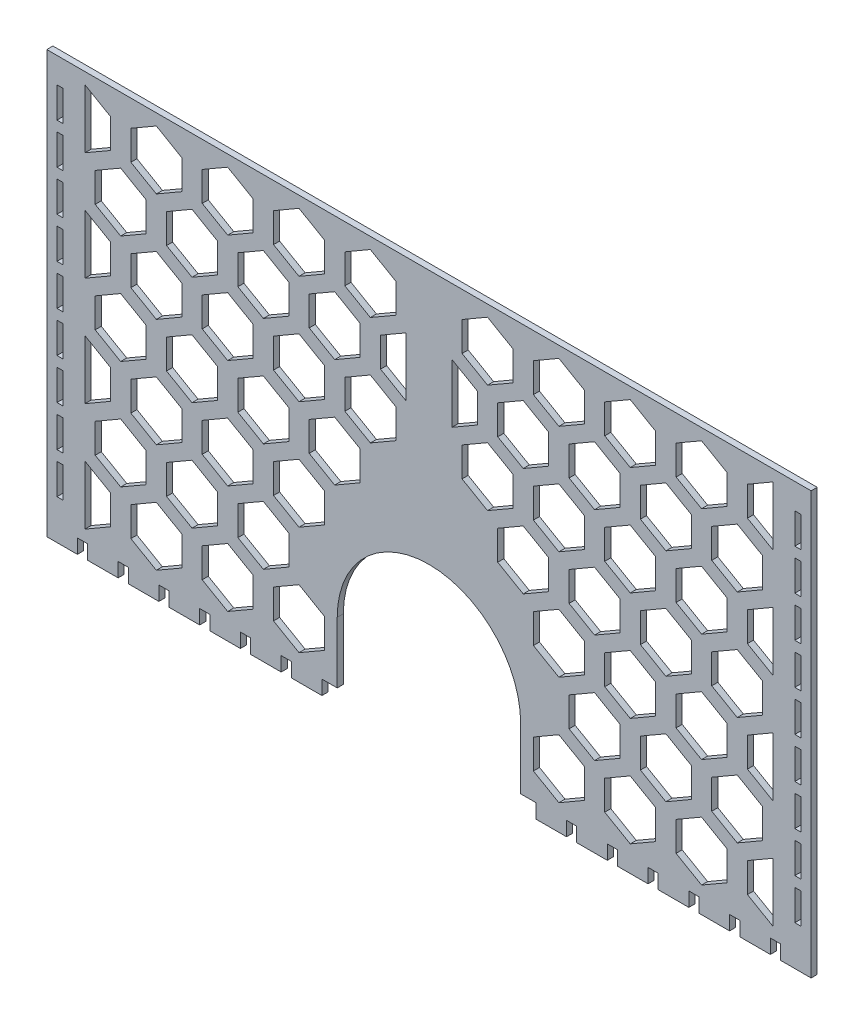
SolidWorks part; units mm, degrees
material "Brass"
ref_plane "Front Plane" through (0, 0, 0) normal (0, 0, 1) x (1, 0, 0)
ref_plane "Top Plane" through (0, 0, 0) normal (0, 1, 0) x (1, 0, 0)
ref_plane "Right Plane" through (0, 0, 0) normal (1, 0, 0) x (0, 0, -1)
sketch "Sketch1" plane through (0, 0, 0) normal (0, 0, 1) x (1, 0, 0)
  line L0 (0, 100) -> (0, -100) construction
  line L2 (-187.5, -100) -> (-187.5, 100)
  line L3 (-187.5, 100) -> (187.5, 100)
  line L4 (187.5, -100) -> (187.5, 100)
  line L6 (-187.5, 0) -> (187.5, 0) construction
  line L11 (-187.5, -100) -> (187.5, -100)
  line L13 (-187.5, 0) -> (-182.5, 0) construction
  line L15 (-45, -70) -> (-45, -100)
  line L16 (-45, -100) -> (45, -100)
  line L17 (45, -70) -> (45, -100)
  line L18 (-179.5, 7.5) -> (-182.5, 7.5)
  line L19 (-179.5, 7.5) -> (-179.5, -7.5)
  line L20 (-179.5, -7.5) -> (-182.5, -7.5)
  line L21 (-182.5, 7.5) -> (-182.5, -7.5)
  line L22 (-179.5, 27.5) -> (-179.5, 12.5)
  line L23 (-179.5, 27.5) -> (-182.5, 27.5)
  line L24 (-182.5, 27.5) -> (-182.5, 12.5)
  line L25 (-179.5, 12.5) -> (-182.5, 12.5)
  line L26 (-179.5, 47.5) -> (-179.5, 32.5)
  line L27 (-179.5, 47.5) -> (-182.5, 47.5)
  line L28 (-182.5, 47.5) -> (-182.5, 32.5)
  line L29 (-179.5, 32.5) -> (-182.5, 32.5)
  line L30 (-179.5, 67.5) -> (-179.5, 52.5)
  line L31 (-179.5, 67.5) -> (-182.5, 67.5)
  line L32 (-182.5, 67.5) -> (-182.5, 52.5)
  line L33 (-179.5, 52.5) -> (-182.5, 52.5)
  line L34 (-179.5, 87.5) -> (-179.5, 72.5)
  line L35 (-179.5, 87.5) -> (-182.5, 87.5)
  line L36 (-182.5, 87.5) -> (-182.5, 72.5)
  line L37 (-179.5, 72.5) -> (-182.5, 72.5)
  line L38 (-179.5, 7.5) -> (-179.5, -7.5)
  line L39 (-179.5, 7.5) -> (-182.5, 7.5)
  line L40 (-182.5, 7.5) -> (-182.5, -7.5)
  line L41 (-179.5, -7.5) -> (-182.5, -7.5)
  line L42 (-179.5, 27.5) -> (-179.5, 12.5)
  line L43 (-179.5, 27.5) -> (-182.5, 27.5)
  line L44 (-182.5, 27.5) -> (-182.5, 12.5)
  line L45 (-179.5, 12.5) -> (-182.5, 12.5)
  line L46 (-179.5, 47.5) -> (-179.5, 32.5)
  line L47 (-179.5, 47.5) -> (-182.5, 47.5)
  line L48 (-182.5, 47.5) -> (-182.5, 32.5)
  line L49 (-179.5, 32.5) -> (-182.5, 32.5)
  line L50 (-179.5, 67.5) -> (-179.5, 52.5)
  line L51 (-179.5, 67.5) -> (-182.5, 67.5)
  line L52 (-182.5, 67.5) -> (-182.5, 52.5)
  line L53 (-179.5, 52.5) -> (-182.5, 52.5)
  line L54 (-179.5, -12.5) -> (-179.5, -27.5)
  line L55 (-179.5, -12.5) -> (-182.5, -12.5)
  line L56 (-182.5, -12.5) -> (-182.5, -27.5)
  line L57 (-179.5, -27.5) -> (-182.5, -27.5)
  line L58 (-179.5, 7.5) -> (-179.5, -7.5)
  line L59 (-179.5, 7.5) -> (-182.5, 7.5)
  line L60 (-182.5, 7.5) -> (-182.5, -7.5)
  line L61 (-179.5, -7.5) -> (-182.5, -7.5)
  line L62 (-179.5, 27.5) -> (-179.5, 12.5)
  line L63 (-179.5, 27.5) -> (-182.5, 27.5)
  line L64 (-182.5, 27.5) -> (-182.5, 12.5)
  line L65 (-179.5, 12.5) -> (-182.5, 12.5)
  line L66 (-179.5, 47.5) -> (-179.5, 32.5)
  line L67 (-179.5, 47.5) -> (-182.5, 47.5)
  line L68 (-182.5, 47.5) -> (-182.5, 32.5)
  line L69 (-179.5, 32.5) -> (-182.5, 32.5)
  line L70 (-179.5, -32.5) -> (-179.5, -47.5)
  line L71 (-179.5, -32.5) -> (-182.5, -32.5)
  line L72 (-182.5, -32.5) -> (-182.5, -47.5)
  line L73 (-179.5, -47.5) -> (-182.5, -47.5)
  line L74 (-179.5, -12.5) -> (-179.5, -27.5)
  line L75 (-179.5, -12.5) -> (-182.5, -12.5)
  line L76 (-182.5, -12.5) -> (-182.5, -27.5)
  line L77 (-179.5, -27.5) -> (-182.5, -27.5)
  line L78 (-179.5, 7.5) -> (-179.5, -7.5)
  line L79 (-179.5, 7.5) -> (-182.5, 7.5)
  line L80 (-182.5, 7.5) -> (-182.5, -7.5)
  line L81 (-179.5, -7.5) -> (-182.5, -7.5)
  line L82 (-179.5, 27.5) -> (-179.5, 12.5)
  line L83 (-179.5, 27.5) -> (-182.5, 27.5)
  line L84 (-182.5, 27.5) -> (-182.5, 12.5)
  line L85 (-179.5, 12.5) -> (-182.5, 12.5)
  line L86 (-179.5, -52.5) -> (-179.5, -67.5)
  line L87 (-179.5, -52.5) -> (-182.5, -52.5)
  line L88 (-182.5, -52.5) -> (-182.5, -67.5)
  line L89 (-179.5, -67.5) -> (-182.5, -67.5)
  line L90 (-179.5, -32.5) -> (-179.5, -47.5)
  line L91 (-179.5, -32.5) -> (-182.5, -32.5)
  line L92 (-182.5, -32.5) -> (-182.5, -47.5)
  line L93 (-179.5, -47.5) -> (-182.5, -47.5)
  line L94 (-179.5, -12.5) -> (-179.5, -27.5)
  line L95 (-179.5, -12.5) -> (-182.5, -12.5)
  line L96 (-182.5, -12.5) -> (-182.5, -27.5)
  line L97 (-179.5, -27.5) -> (-182.5, -27.5)
  line L98 (-179.5, 7.5) -> (-179.5, -7.5)
  line L99 (-179.5, 7.5) -> (-182.5, 7.5)
  line L100 (-182.5, 7.5) -> (-182.5, -7.5)
  line L101 (-179.5, -7.5) -> (-182.5, -7.5)
  line L102 (-179.5, -12.5) -> (-179.5, -27.5)
  line L103 (-179.5, -12.5) -> (-182.5, -12.5)
  line L104 (-182.5, -12.5) -> (-182.5, -27.5)
  line L105 (-179.5, -27.5) -> (-182.5, -27.5)
  line L106 (-179.5, -32.5) -> (-179.5, -47.5)
  line L107 (-179.5, -32.5) -> (-182.5, -32.5)
  line L108 (-182.5, -32.5) -> (-182.5, -47.5)
  line L109 (-179.5, -47.5) -> (-182.5, -47.5)
  line L110 (-179.5, -52.5) -> (-179.5, -67.5)
  line L111 (-179.5, -52.5) -> (-182.5, -52.5)
  line L112 (-182.5, -52.5) -> (-182.5, -67.5)
  line L113 (-179.5, -67.5) -> (-182.5, -67.5)
  line L114 (-179.5, -72.5) -> (-179.5, -87.5)
  line L115 (-179.5, -72.5) -> (-182.5, -72.5)
  line L116 (-182.5, -72.5) -> (-182.5, -87.5)
  line L117 (-179.5, -87.5) -> (-182.5, -87.5)
  line L118 (187.5, 0) -> (182.5, 0) construction
  line L119 (182.5, 27.5) -> (179.5, 27.5)
  line L120 (179.5, 27.5) -> (179.5, 12.5)
  line L121 (182.5, 7.5) -> (179.5, 7.5)
  line L122 (182.5, 7.5) -> (182.5, -7.5)
  line L123 (182.5, -7.5) -> (179.5, -7.5)
  line L124 (179.5, 7.5) -> (179.5, -7.5)
  line L221 (182.5, 12.5) -> (179.5, 12.5)
  line L222 (182.5, 27.5) -> (182.5, 12.5)
  line L223 (182.5, 47.5) -> (179.5, 47.5)
  line L224 (179.5, 47.5) -> (179.5, 32.5)
  line L225 (182.5, 32.5) -> (179.5, 32.5)
  line L226 (182.5, 47.5) -> (182.5, 32.5)
  line L227 (182.5, 67.5) -> (179.5, 67.5)
  line L228 (179.5, 67.5) -> (179.5, 52.5)
  line L229 (182.5, 52.5) -> (179.5, 52.5)
  line L230 (182.5, 67.5) -> (182.5, 52.5)
  line L231 (182.5, 87.5) -> (179.5, 87.5)
  line L232 (179.5, 87.5) -> (179.5, 72.5)
  line L233 (182.5, 72.5) -> (179.5, 72.5)
  line L234 (182.5, 87.5) -> (182.5, 72.5)
  line L235 (182.5, -12.5) -> (179.5, -12.5)
  line L236 (179.5, -12.5) -> (179.5, -27.5)
  line L237 (182.5, -27.5) -> (179.5, -27.5)
  line L238 (182.5, -12.5) -> (182.5, -27.5)
  line L239 (182.5, -32.5) -> (179.5, -32.5)
  line L240 (179.5, -32.5) -> (179.5, -47.5)
  line L241 (182.5, -47.5) -> (179.5, -47.5)
  line L242 (182.5, -32.5) -> (182.5, -47.5)
  line L243 (182.5, -52.5) -> (179.5, -52.5)
  line L244 (179.5, -52.5) -> (179.5, -67.5)
  line L245 (182.5, -67.5) -> (179.5, -67.5)
  line L246 (182.5, -52.5) -> (182.5, -67.5)
  line L247 (182.5, -72.5) -> (179.5, -72.5)
  line L248 (179.5, -72.5) -> (179.5, -87.5)
  line L249 (182.5, -87.5) -> (179.5, -87.5)
  line L250 (182.5, -72.5) -> (182.5, -87.5)
  arc A1 (45, -70) -> (-45, -70) centre (0, -70) ccw
  circle A2 centre (0, -70) radius 40 construction
  point P0 (0, 0)
  point P16 (0, 0)
  point P17 (-182.5, 0)
  point P121 (182.5, 0)
  point P122 (181, 7.5)
  dimension "D3" = 90
  dimension "D5" = 30
  dimension "D4" = 142.5
  dimension "D6" = 80
  dimension "D2" = 187.5
  dimension "D7" = 15
  dimension "D8" = 3
  dimension "D9" = 5
  dimension "D12" = 5
  dimension "D13" = 5
  dimension "D14" = 200
  dimension "D15" = 15
  dimension "D16" = 3
  dimension "D17" = 5
  dimension "D18" = 5
  dimension "D19" = 5
  dimension "D21" = 5
  dimension "D10" = 5
  dimension "D11" = 5
  dimension "D20" = 5
extrude "Boss-Extrude1" add sketch "Sketch1" along normal blind 3 contours A1 L17 L11 L4 L3 L2 L15 region at (0, 5.73, 0)
sketch "Sketch7" plane through (0, -100, 0) normal (0, -1, 0) x (1, 0, 0)
  line L0 (-187.5, 0) -> (-45, 0) construction
  line L1 (-187.5, 3) -> (-172.5, 3)
  line L2 (-187.5, 3) -> (-187.5, 0)
  line L3 (-187.5, 0) -> (-172.5, 0)
  line L4 (-172.5, 3) -> (-172.5, 0)
  line L5 (-167.5, 3) -> (-167.5, 0)
  line L6 (-167.5, 3) -> (-152.5, 3)
  line L7 (-152.5, 3) -> (-152.5, 0)
  line L8 (-167.5, 0) -> (-152.5, 0)
  line L9 (-147.5, 3) -> (-147.5, 0)
  line L10 (-147.5, 3) -> (-132.5, 3)
  line L11 (-132.5, 3) -> (-132.5, 0)
  line L12 (-147.5, 0) -> (-132.5, 0)
  line L13 (-127.5, 3) -> (-127.5, 0)
  line L14 (-127.5, 3) -> (-112.5, 3)
  line L15 (-112.5, 3) -> (-112.5, 0)
  line L16 (-127.5, 0) -> (-112.5, 0)
  line L17 (-107.5, 3) -> (-107.5, 0)
  line L18 (-107.5, 3) -> (-92.5, 3)
  line L19 (-92.5, 3) -> (-92.5, 0)
  line L20 (-107.5, 0) -> (-92.5, 0)
  line L21 (-87.5, 3) -> (-87.5, 0)
  line L22 (-87.5, 3) -> (-72.5, 3)
  line L23 (-72.5, 3) -> (-72.5, 0)
  line L24 (-87.5, 0) -> (-72.5, 0)
  line L25 (-67.5, 3) -> (-67.5, 0)
  line L26 (-67.5, 3) -> (-52.5, 3)
  line L27 (-52.5, 3) -> (-52.5, 0)
  line L28 (-67.5, 0) -> (-52.5, 0)
  dimension "D1" = 15
  dimension "D3" = 5
  dimension "D2" = 7
extrude "Boss-Extrude2" add sketch "Sketch7" along normal blind 7
sketch "Sketch8" plane through (0, -100, 0) normal (0, -1, 0) x (1, 0, 0)
  line L0 (45, 3) -> (187.5, 3) construction
  line L1 (187.5, 0) -> (172.5, 0)
  line L2 (187.5, 0) -> (187.5, 3)
  line L3 (187.5, 3) -> (172.5, 3)
  line L4 (172.5, 0) -> (172.5, 3)
  line L5 (167.5, 0) -> (167.5, 3)
  line L6 (167.5, 0) -> (152.5, 0)
  line L7 (152.5, 0) -> (152.5, 3)
  line L8 (167.5, 3) -> (152.5, 3)
  line L9 (147.5, 0) -> (147.5, 3)
  line L10 (147.5, 0) -> (132.5, 0)
  line L11 (132.5, 0) -> (132.5, 3)
  line L12 (147.5, 3) -> (132.5, 3)
  line L13 (127.5, 0) -> (127.5, 3)
  line L14 (127.5, 0) -> (112.5, 0)
  line L15 (112.5, 0) -> (112.5, 3)
  line L16 (127.5, 3) -> (112.5, 3)
  line L17 (107.5, 0) -> (107.5, 3)
  line L18 (107.5, 0) -> (92.5, 0)
  line L19 (92.5, 0) -> (92.5, 3)
  line L20 (107.5, 3) -> (92.5, 3)
  line L21 (87.5, 0) -> (87.5, 3)
  line L22 (87.5, 0) -> (72.5, 0)
  line L23 (72.5, 0) -> (72.5, 3)
  line L24 (87.5, 3) -> (72.5, 3)
  line L25 (67.5, 0) -> (67.5, 3)
  line L26 (67.5, 0) -> (52.5, 0)
  line L27 (52.5, 0) -> (52.5, 3)
  line L28 (67.5, 3) -> (52.5, 3)
  dimension "D1" = 15
  dimension "D3" = 5
  dimension "D2" = 7
extrude "Boss-Extrude3" add sketch "Sketch8" along normal blind 7
sketch "Sketch10" plane through (0, 0, 0) normal (0, 0, -1) x (-1, 0, 0)
  line L0 (-45, -100) -> (-45, 100) construction
  line L1 (187.5, 100) -> (-187.5, 100) construction
  line L2 (-45, 100) -> (-187.5, 100) construction
  line L3 (-187.5, 100) -> (-187.5, -100) construction
  line L4 (-187.5, -107) -> (-187.5, 100) construction
  line L5 (-187.5, -100) -> (-45, -100) construction
  line L6 (-116.25, 100) -> (-116.25, -100) construction
  line L7 (-98.75, -26.6506) -> (-98.75, -100) construction
  line L8 (-45, 0) -> (-187.5, 0) construction
  line L9 (-116.25, -14.4338) -> (-103.75, -7.2169)
  line L10 (-103.75, -7.2169) -> (-103.75, 7.2169)
  line L11 (-103.75, 7.2169) -> (-116.25, 14.4338)
  line L12 (-116.25, 14.4338) -> (-128.75, 7.2169)
  line L13 (-128.75, 7.2169) -> (-128.75, -7.2169)
  line L14 (-128.75, -7.2169) -> (-116.25, -14.4338)
  line L15 (-98.75, -100) -> (-98.75, 100) construction
  line L16 (-98.75, -12.2169) -> (-111.25, -19.4338)
  line L17 (-111.25, -19.4338) -> (-111.25, -33.8675)
  line L18 (-111.25, -33.8675) -> (-98.75, -41.0844)
  line L19 (-98.75, -41.0844) -> (-86.25, -33.8675)
  line L20 (-86.25, -33.8675) -> (-86.25, -19.4338)
  line L21 (-86.25, -19.4338) -> (-98.75, -12.2169)
  line L22 (-133.75, -100) -> (-133.75, 100) construction
  line L23 (-45, -26.6506) -> (-187.5, -26.6506) construction
  line L24 (-133.75, -41.0844) -> (-121.25, -33.8675)
  line L25 (-121.25, -33.8675) -> (-121.25, -19.4338)
  line L26 (-121.25, -19.4338) -> (-133.75, -12.2169)
  line L27 (-133.75, -12.2169) -> (-146.25, -19.4338)
  line L28 (-146.25, -19.4338) -> (-146.25, -33.8675)
  line L29 (-146.25, -33.8675) -> (-133.75, -41.0844)
  line L36 (187.5, -107) -> (187.5, 100) construction
  line L37 (-116.25, -67.735) -> (-103.75, -60.5181)
  line L38 (-103.75, -60.5181) -> (-103.75, -46.0844)
  line L39 (-103.75, -46.0844) -> (-116.25, -38.8675)
  line L40 (-116.25, -38.8675) -> (-128.75, -46.0844)
  line L41 (-128.75, -46.0844) -> (-128.75, -60.5181)
  line L42 (-128.75, -60.5181) -> (-116.25, -67.735)
  line L61 (-81.25, -14.4338) -> (-68.75, -7.2169)
  line L62 (-68.75, -7.2169) -> (-68.75, 7.2169)
  line L63 (-68.75, 7.2169) -> (-81.25, 14.4338)
  line L64 (-81.25, 14.4338) -> (-93.75, 7.2169)
  line L65 (-93.75, 7.2169) -> (-93.75, -7.2169)
  line L66 (-93.75, -7.2169) -> (-81.25, -14.4338)
  line L67 (-81.25, -67.735) -> (-68.75, -60.5181)
  line L68 (-68.75, -60.5181) -> (-68.75, -46.0844)
  line L69 (-68.75, -46.0844) -> (-81.25, -38.8675)
  line L70 (-81.25, -38.8675) -> (-93.75, -46.0844)
  line L71 (-93.75, -46.0844) -> (-93.75, -60.5181)
  line L72 (-93.75, -60.5181) -> (-81.25, -67.735)
  line L73 (-63.75, -41.0844) -> (-51.25, -33.8675)
  line L74 (-51.25, -33.8675) -> (-51.25, -19.4338)
  line L75 (-51.25, -19.4338) -> (-63.75, -12.2169)
  line L76 (-63.75, -12.2169) -> (-76.25, -19.4338)
  line L77 (-76.25, -19.4338) -> (-76.25, -33.8675)
  line L78 (-76.25, -33.8675) -> (-63.75, -41.0844)
  line L79 (-151.25, -14.4338) -> (-138.75, -7.2169)
  line L80 (-138.75, -7.2169) -> (-138.75, 7.2169)
  line L81 (-138.75, 7.2169) -> (-151.25, 14.4338)
  line L82 (-151.25, 14.4338) -> (-163.75, 7.2169)
  line L83 (-163.75, 7.2169) -> (-163.75, -7.2169)
  line L84 (-163.75, -7.2169) -> (-151.25, -14.4338)
  line L85 (-151.25, -67.735) -> (-138.75, -60.5181)
  line L86 (-138.75, -60.5181) -> (-138.75, -46.0844)
  line L87 (-138.75, -46.0844) -> (-151.25, -38.8675)
  line L88 (-151.25, -38.8675) -> (-163.75, -46.0844)
  line L89 (-163.75, -46.0844) -> (-163.75, -60.5181)
  line L90 (-163.75, -60.5181) -> (-151.25, -67.735)
  line L91 (-168.75, -41.0844) -> (-156.25, -33.8675)
  line L92 (-156.25, -33.8675) -> (-156.25, -19.4338)
  line L93 (-156.25, -19.4338) -> (-168.75, -12.2169)
  line L96 (-168.75, -12.2169) -> (-168.75, -41.0844)
  line L103 (-133.75, 12.2169) -> (-121.25, 19.4338)
  line L104 (-121.25, 19.4338) -> (-121.25, 33.8675)
  line L105 (-121.25, 33.8675) -> (-133.75, 41.0844)
  line L106 (-133.75, 41.0844) -> (-146.25, 33.8675)
  line L107 (-146.25, 33.8675) -> (-146.25, 19.4338)
  line L108 (-146.25, 19.4338) -> (-133.75, 12.2169)
  line L109 (-98.75, 12.2169) -> (-86.25, 19.4338)
  line L110 (-86.25, 19.4338) -> (-86.25, 33.8675)
  line L111 (-86.25, 33.8675) -> (-98.75, 41.0844)
  line L112 (-98.75, 41.0844) -> (-111.25, 33.8675)
  line L113 (-111.25, 33.8675) -> (-111.25, 19.4338)
  line L114 (-111.25, 19.4338) -> (-98.75, 12.2169)
  line L115 (-168.75, 12.2169) -> (-156.25, 19.4338)
  line L116 (-156.25, 19.4338) -> (-156.25, 33.8675)
  line L117 (-156.25, 33.8675) -> (-168.75, 41.0844)
  line L118 (-168.75, 41.0844) -> (-168.75, 12.2169)
  line L119 (-63.75, 12.2169) -> (-51.25, 19.4338)
  line L120 (-51.25, 19.4338) -> (-51.25, 33.8675)
  line L121 (-51.25, 33.8675) -> (-63.75, 41.0844)
  line L122 (-63.75, 41.0844) -> (-76.25, 33.8675)
  line L123 (-76.25, 33.8675) -> (-76.25, 19.4338)
  line L124 (-76.25, 19.4338) -> (-63.75, 12.2169)
  line L125 (-28.75, 12.2169) -> (-16.25, 19.4338)
  line L126 (-16.25, 19.4338) -> (-16.25, 33.8675)
  line L127 (-16.25, 33.8675) -> (-28.75, 41.0844)
  line L128 (-28.75, 41.0844) -> (-41.25, 33.8675)
  line L129 (-41.25, 33.8675) -> (-41.25, 19.4338)
  line L130 (-41.25, 19.4338) -> (-28.75, 12.2169)
  line L131 (-46.25, -14.4338) -> (-33.75, -7.2169)
  line L132 (-33.75, -7.2169) -> (-33.75, 7.2169)
  line L133 (-33.75, 7.2169) -> (-46.25, 14.4338)
  line L134 (-46.25, 14.4338) -> (-58.75, 7.2169)
  line L135 (-58.75, 7.2169) -> (-58.75, -7.2169)
  line L136 (-58.75, -7.2169) -> (-46.25, -14.4338)
  line L137 (0, -25) -> (0, 100) construction
  line L138 (-133.75, -94.3857) -> (-121.25, -87.1688)
  line L139 (-121.25, -87.1688) -> (-121.25, -72.735)
  line L140 (-121.25, -72.735) -> (-133.75, -65.5181)
  line L141 (-133.75, -65.5181) -> (-146.25, -72.735)
  line L142 (-146.25, -72.735) -> (-146.25, -87.1688)
  line L143 (-146.25, -87.1688) -> (-133.75, -94.3857)
  line L144 (-98.75, -94.3857) -> (-86.25, -87.1688)
  line L145 (-86.25, -87.1688) -> (-86.25, -72.735)
  line L146 (-86.25, -72.735) -> (-98.75, -65.5181)
  line L147 (-98.75, -65.5181) -> (-111.25, -72.735)
  line L148 (-111.25, -72.735) -> (-111.25, -87.1688)
  line L149 (-111.25, -87.1688) -> (-98.75, -94.3857)
  line L150 (-63.75, -94.3857) -> (-51.25, -87.1688)
  line L151 (-51.25, -87.1688) -> (-51.25, -72.735)
  line L152 (-51.25, -72.735) -> (-63.75, -65.5181)
  line L153 (-63.75, -65.5181) -> (-76.25, -72.735)
  line L154 (-76.25, -72.735) -> (-76.25, -87.1688)
  line L155 (-76.25, -87.1688) -> (-63.75, -94.3857)
  line L156 (-168.75, -94.3857) -> (-156.25, -87.1688)
  line L157 (-156.25, -87.1688) -> (-156.25, -72.735)
  line L158 (-156.25, -72.735) -> (-168.75, -65.5181)
  line L159 (-168.75, -65.5181) -> (-168.75, -94.3857)
  line L160 (-151.25, 38.8675) -> (-138.75, 46.0844)
  line L161 (-138.75, 46.0844) -> (-138.75, 60.5181)
  line L162 (-138.75, 60.5181) -> (-151.25, 67.735)
  line L163 (-151.25, 67.735) -> (-163.75, 60.5181)
  line L164 (-163.75, 60.5181) -> (-163.75, 46.0844)
  line L165 (-163.75, 46.0844) -> (-151.25, 38.8675)
  line L166 (-116.25, 38.8675) -> (-103.75, 46.0844)
  line L167 (-103.75, 46.0844) -> (-103.75, 60.5181)
  line L168 (-103.75, 60.5181) -> (-116.25, 67.735)
  line L169 (-116.25, 67.735) -> (-128.75, 60.5181)
  line L170 (-128.75, 60.5181) -> (-128.75, 46.0844)
  line L171 (-128.75, 46.0844) -> (-116.25, 38.8675)
  line L172 (-81.25, 38.8675) -> (-68.75, 46.0844)
  line L173 (-68.75, 46.0844) -> (-68.75, 60.5181)
  line L174 (-68.75, 60.5181) -> (-81.25, 67.735)
  line L175 (-81.25, 67.735) -> (-93.75, 60.5181)
  line L176 (-93.75, 60.5181) -> (-93.75, 46.0844)
  line L177 (-93.75, 46.0844) -> (-81.25, 38.8675)
  line L178 (-46.25, 38.8675) -> (-33.75, 46.0844)
  line L179 (-33.75, 46.0844) -> (-33.75, 60.5181)
  line L180 (-33.75, 60.5181) -> (-46.25, 67.735)
  line L181 (-46.25, 67.735) -> (-58.75, 60.5181)
  line L182 (-58.75, 60.5181) -> (-58.75, 46.0844)
  line L183 (-58.75, 46.0844) -> (-46.25, 38.8675)
  line L187 (-11.25, 67.735) -> (-23.75, 60.5181)
  line L188 (-23.75, 60.5181) -> (-23.75, 46.0844)
  line L189 (-23.75, 46.0844) -> (-11.25, 38.8675)
  line L190 (-11.25, 67.735) -> (-11.25, 38.8675)
  line L191 (-133.75, 65.5181) -> (-121.25, 72.735)
  line L192 (-121.25, 72.735) -> (-121.25, 87.1688)
  line L193 (-121.25, 87.1688) -> (-133.75, 94.3857)
  line L194 (-133.75, 94.3857) -> (-146.25, 87.1688)
  line L195 (-146.25, 87.1688) -> (-146.25, 72.735)
  line L196 (-146.25, 72.735) -> (-133.75, 65.5181)
  line L197 (-98.75, 65.5181) -> (-86.25, 72.735)
  line L198 (-86.25, 72.735) -> (-86.25, 87.1688)
  line L199 (-86.25, 87.1688) -> (-98.75, 94.3857)
  line L200 (-98.75, 94.3857) -> (-111.25, 87.1688)
  line L201 (-111.25, 87.1688) -> (-111.25, 72.735)
  line L202 (-111.25, 72.735) -> (-98.75, 65.5181)
  line L203 (-168.75, 65.5181) -> (-156.25, 72.735)
  line L204 (-156.25, 72.735) -> (-156.25, 87.1688)
  line L205 (-156.25, 87.1688) -> (-168.75, 94.3857)
  line L206 (-168.75, 94.3857) -> (-168.75, 65.5181)
  line L207 (-63.75, 65.5181) -> (-51.25, 72.735)
  line L208 (-51.25, 72.735) -> (-51.25, 87.1688)
  line L209 (-51.25, 87.1688) -> (-63.75, 94.3857)
  line L210 (-63.75, 94.3857) -> (-76.25, 87.1688)
  line L211 (-76.25, 87.1688) -> (-76.25, 72.735)
  line L212 (-76.25, 72.735) -> (-63.75, 65.5181)
  line L213 (-28.75, 65.5181) -> (-16.25, 72.735)
  line L214 (-16.25, 72.735) -> (-16.25, 87.1688)
  line L215 (-16.25, 87.1688) -> (-28.75, 94.3857)
  line L216 (-28.75, 94.3857) -> (-41.25, 87.1688)
  line L217 (-41.25, 87.1688) -> (-41.25, 72.735)
  line L218 (-41.25, 72.735) -> (-28.75, 65.5181)
  line L219 (45, -26.6506) -> (187.5, -26.6506) construction
  line L220 (133.75, -100) -> (133.75, 100) construction
  line L221 (98.75, -100) -> (98.75, 100) construction
  line L222 (45, 0) -> (187.5, 0) construction
  line L223 (98.75, -26.6506) -> (98.75, -100) construction
  line L224 (116.25, 100) -> (116.25, -100) construction
  line L225 (187.5, -100) -> (45, -100) construction
  line L226 (187.5, 100) -> (187.5, -100) construction
  line L227 (45, 100) -> (187.5, 100) construction
  line L228 (45, -100) -> (45, 100) construction
  line L229 (41.25, 72.735) -> (28.75, 65.5181)
  line L230 (41.25, 87.1688) -> (41.25, 72.735)
  line L231 (28.75, 94.3857) -> (41.25, 87.1688)
  line L232 (16.25, 87.1688) -> (28.75, 94.3857)
  line L233 (16.25, 72.735) -> (16.25, 87.1688)
  line L234 (28.75, 65.5181) -> (16.25, 72.735)
  line L235 (76.25, 72.735) -> (63.75, 65.5181)
  line L236 (76.25, 87.1688) -> (76.25, 72.735)
  line L237 (63.75, 94.3857) -> (76.25, 87.1688)
  line L238 (51.25, 87.1688) -> (63.75, 94.3857)
  line L239 (51.25, 72.735) -> (51.25, 87.1688)
  line L240 (63.75, 65.5181) -> (51.25, 72.735)
  line L241 (168.75, 94.3857) -> (168.75, 65.5181)
  line L242 (156.25, 87.1688) -> (168.75, 94.3857)
  line L243 (156.25, 72.735) -> (156.25, 87.1688)
  line L244 (168.75, 65.5181) -> (156.25, 72.735)
  line L245 (111.25, 72.735) -> (98.75, 65.5181)
  line L246 (111.25, 87.1688) -> (111.25, 72.735)
  line L247 (98.75, 94.3857) -> (111.25, 87.1688)
  line L248 (86.25, 87.1688) -> (98.75, 94.3857)
  line L249 (86.25, 72.735) -> (86.25, 87.1688)
  line L250 (98.75, 65.5181) -> (86.25, 72.735)
  line L251 (146.25, 72.735) -> (133.75, 65.5181)
  line L252 (146.25, 87.1688) -> (146.25, 72.735)
  line L253 (133.75, 94.3857) -> (146.25, 87.1688)
  line L254 (121.25, 87.1688) -> (133.75, 94.3857)
  line L255 (121.25, 72.735) -> (121.25, 87.1688)
  line L256 (133.75, 65.5181) -> (121.25, 72.735)
  line L257 (11.25, 67.735) -> (11.25, 38.8675)
  line L258 (23.75, 46.0844) -> (11.25, 38.8675)
  line L259 (23.75, 60.5181) -> (23.75, 46.0844)
  line L260 (11.25, 67.735) -> (23.75, 60.5181)
  line L261 (58.75, 46.0844) -> (46.25, 38.8675)
  line L262 (58.75, 60.5181) -> (58.75, 46.0844)
  line L263 (46.25, 67.735) -> (58.75, 60.5181)
  line L264 (33.75, 60.5181) -> (46.25, 67.735)
  line L265 (33.75, 46.0844) -> (33.75, 60.5181)
  line L266 (46.25, 38.8675) -> (33.75, 46.0844)
  line L267 (93.75, 46.0844) -> (81.25, 38.8675)
  line L268 (93.75, 60.5181) -> (93.75, 46.0844)
  line L269 (81.25, 67.735) -> (93.75, 60.5181)
  line L270 (68.75, 60.5181) -> (81.25, 67.735)
  line L271 (68.75, 46.0844) -> (68.75, 60.5181)
  line L272 (81.25, 38.8675) -> (68.75, 46.0844)
  line L273 (128.75, 46.0844) -> (116.25, 38.8675)
  line L274 (128.75, 60.5181) -> (128.75, 46.0844)
  line L275 (116.25, 67.735) -> (128.75, 60.5181)
  line L276 (103.75, 60.5181) -> (116.25, 67.735)
  line L277 (103.75, 46.0844) -> (103.75, 60.5181)
  line L278 (116.25, 38.8675) -> (103.75, 46.0844)
  line L279 (163.75, 46.0844) -> (151.25, 38.8675)
  line L280 (163.75, 60.5181) -> (163.75, 46.0844)
  line L281 (151.25, 67.735) -> (163.75, 60.5181)
  line L282 (138.75, 60.5181) -> (151.25, 67.735)
  line L283 (138.75, 46.0844) -> (138.75, 60.5181)
  line L284 (151.25, 38.8675) -> (138.75, 46.0844)
  line L285 (168.75, -65.5181) -> (168.75, -94.3857)
  line L286 (156.25, -72.735) -> (168.75, -65.5181)
  line L287 (156.25, -87.1688) -> (156.25, -72.735)
  line L288 (168.75, -94.3857) -> (156.25, -87.1688)
  line L289 (76.25, -87.1688) -> (63.75, -94.3857)
  line L290 (76.25, -72.735) -> (76.25, -87.1688)
  line L291 (63.75, -65.5181) -> (76.25, -72.735)
  line L292 (51.25, -72.735) -> (63.75, -65.5181)
  line L293 (51.25, -87.1688) -> (51.25, -72.735)
  line L294 (63.75, -94.3857) -> (51.25, -87.1688)
  line L295 (111.25, -87.1688) -> (98.75, -94.3857)
  line L296 (111.25, -72.735) -> (111.25, -87.1688)
  line L297 (98.75, -65.5181) -> (111.25, -72.735)
  line L298 (86.25, -72.735) -> (98.75, -65.5181)
  line L299 (86.25, -87.1688) -> (86.25, -72.735)
  line L300 (98.75, -94.3857) -> (86.25, -87.1688)
  line L301 (146.25, -87.1688) -> (133.75, -94.3857)
  line L302 (146.25, -72.735) -> (146.25, -87.1688)
  line L303 (133.75, -65.5181) -> (146.25, -72.735)
  line L304 (121.25, -72.735) -> (133.75, -65.5181)
  line L305 (121.25, -87.1688) -> (121.25, -72.735)
  line L306 (133.75, -94.3857) -> (121.25, -87.1688)
  line L307 (58.75, -7.2169) -> (46.25, -14.4338)
  line L308 (58.75, 7.2169) -> (58.75, -7.2169)
  line L309 (46.25, 14.4338) -> (58.75, 7.2169)
  line L310 (33.75, 7.2169) -> (46.25, 14.4338)
  line L311 (33.75, -7.2169) -> (33.75, 7.2169)
  line L312 (46.25, -14.4338) -> (33.75, -7.2169)
  line L313 (41.25, 19.4338) -> (28.75, 12.2169)
  line L314 (41.25, 33.8675) -> (41.25, 19.4338)
  line L315 (28.75, 41.0844) -> (41.25, 33.8675)
  line L316 (16.25, 33.8675) -> (28.75, 41.0844)
  line L317 (16.25, 19.4338) -> (16.25, 33.8675)
  line L318 (28.75, 12.2169) -> (16.25, 19.4338)
  line L319 (76.25, 19.4338) -> (63.75, 12.2169)
  line L320 (76.25, 33.8675) -> (76.25, 19.4338)
  line L321 (63.75, 41.0844) -> (76.25, 33.8675)
  line L322 (51.25, 33.8675) -> (63.75, 41.0844)
  line L323 (51.25, 19.4338) -> (51.25, 33.8675)
  line L324 (63.75, 12.2169) -> (51.25, 19.4338)
  line L325 (168.75, 41.0844) -> (168.75, 12.2169)
  line L326 (156.25, 33.8675) -> (168.75, 41.0844)
  line L327 (156.25, 19.4338) -> (156.25, 33.8675)
  line L328 (168.75, 12.2169) -> (156.25, 19.4338)
  line L329 (111.25, 19.4338) -> (98.75, 12.2169)
  line L330 (111.25, 33.8675) -> (111.25, 19.4338)
  line L331 (98.75, 41.0844) -> (111.25, 33.8675)
  line L332 (86.25, 33.8675) -> (98.75, 41.0844)
  line L333 (86.25, 19.4338) -> (86.25, 33.8675)
  line L334 (98.75, 12.2169) -> (86.25, 19.4338)
  line L335 (146.25, 19.4338) -> (133.75, 12.2169)
  line L336 (146.25, 33.8675) -> (146.25, 19.4338)
  line L337 (133.75, 41.0844) -> (146.25, 33.8675)
  line L338 (121.25, 33.8675) -> (133.75, 41.0844)
  line L339 (121.25, 19.4338) -> (121.25, 33.8675)
  line L340 (133.75, 12.2169) -> (121.25, 19.4338)
  line L341 (168.75, -12.2169) -> (168.75, -41.0844)
  line L342 (156.25, -19.4338) -> (168.75, -12.2169)
  line L343 (156.25, -33.8675) -> (156.25, -19.4338)
  line L344 (168.75, -41.0844) -> (156.25, -33.8675)
  line L345 (163.75, -60.5181) -> (151.25, -67.735)
  line L346 (163.75, -46.0844) -> (163.75, -60.5181)
  line L347 (151.25, -38.8675) -> (163.75, -46.0844)
  line L348 (138.75, -46.0844) -> (151.25, -38.8675)
  line L349 (138.75, -60.5181) -> (138.75, -46.0844)
  line L350 (151.25, -67.735) -> (138.75, -60.5181)
  line L351 (163.75, -7.2169) -> (151.25, -14.4338)
  line L352 (163.75, 7.2169) -> (163.75, -7.2169)
  line L353 (151.25, 14.4338) -> (163.75, 7.2169)
  line L354 (138.75, 7.2169) -> (151.25, 14.4338)
  line L355 (138.75, -7.2169) -> (138.75, 7.2169)
  line L356 (151.25, -14.4338) -> (138.75, -7.2169)
  line L357 (76.25, -33.8675) -> (63.75, -41.0844)
  line L358 (76.25, -19.4338) -> (76.25, -33.8675)
  line L359 (63.75, -12.2169) -> (76.25, -19.4338)
  line L360 (51.25, -19.4338) -> (63.75, -12.2169)
  line L361 (51.25, -33.8675) -> (51.25, -19.4338)
  line L362 (63.75, -41.0844) -> (51.25, -33.8675)
  line L363 (93.75, -60.5181) -> (81.25, -67.735)
  line L364 (93.75, -46.0844) -> (93.75, -60.5181)
  line L365 (81.25, -38.8675) -> (93.75, -46.0844)
  line L366 (68.75, -46.0844) -> (81.25, -38.8675)
  line L367 (68.75, -60.5181) -> (68.75, -46.0844)
  line L368 (81.25, -67.735) -> (68.75, -60.5181)
  line L369 (93.75, -7.2169) -> (81.25, -14.4338)
  line L370 (93.75, 7.2169) -> (93.75, -7.2169)
  line L371 (81.25, 14.4338) -> (93.75, 7.2169)
  line L372 (68.75, 7.2169) -> (81.25, 14.4338)
  line L373 (68.75, -7.2169) -> (68.75, 7.2169)
  line L374 (81.25, -14.4338) -> (68.75, -7.2169)
  line L375 (128.75, -60.5181) -> (116.25, -67.735)
  line L376 (128.75, -46.0844) -> (128.75, -60.5181)
  line L377 (116.25, -38.8675) -> (128.75, -46.0844)
  line L378 (103.75, -46.0844) -> (116.25, -38.8675)
  line L379 (103.75, -60.5181) -> (103.75, -46.0844)
  line L380 (116.25, -67.735) -> (103.75, -60.5181)
  line L381 (146.25, -33.8675) -> (133.75, -41.0844)
  line L382 (146.25, -19.4338) -> (146.25, -33.8675)
  line L383 (133.75, -12.2169) -> (146.25, -19.4338)
  line L384 (121.25, -19.4338) -> (133.75, -12.2169)
  line L385 (121.25, -33.8675) -> (121.25, -19.4338)
  line L386 (133.75, -41.0844) -> (121.25, -33.8675)
  line L387 (86.25, -19.4338) -> (98.75, -12.2169)
  line L388 (86.25, -33.8675) -> (86.25, -19.4338)
  line L389 (98.75, -41.0844) -> (86.25, -33.8675)
  line L390 (111.25, -33.8675) -> (98.75, -41.0844)
  line L391 (111.25, -19.4338) -> (111.25, -33.8675)
  line L392 (98.75, -12.2169) -> (111.25, -19.4338)
  line L393 (128.75, -7.2169) -> (116.25, -14.4338)
  line L394 (128.75, 7.2169) -> (128.75, -7.2169)
  line L395 (116.25, 14.4338) -> (128.75, 7.2169)
  line L396 (103.75, 7.2169) -> (116.25, 14.4338)
  line L397 (103.75, -7.2169) -> (103.75, 7.2169)
  line L398 (116.25, -14.4338) -> (103.75, -7.2169)
  circle A0 centre (-116.25, 0) radius 12.5 construction
  circle A1 centre (-98.75, -26.6506) radius 12.5 construction
  circle A2 centre (-133.75, -26.6506) radius 12.5 construction
  circle A3 centre (-116.25, -53.3013) radius 12.5 construction
  circle A7 centre (-81.25, 0) radius 12.5 construction
  circle A8 centre (-81.25, -53.3013) radius 12.5 construction
  circle A9 centre (-63.75, -26.6506) radius 12.5 construction
  circle A10 centre (-151.25, 0) radius 12.5 construction
  circle A11 centre (-151.25, -53.3013) radius 12.5 construction
  arc A12 (-162.5, -37.476) -> (-162.5, -15.8253) centre (-168.75, -26.6506) ccw construction
  circle A14 centre (-133.75, 26.6506) radius 12.5 construction
  circle A15 centre (-98.75, 26.6506) radius 12.5 construction
  arc A16 (-162.5, 15.8253) -> (-162.5, 37.476) centre (-168.75, 26.6506) ccw construction
  circle A17 centre (-63.75, 26.6506) radius 12.5 construction
  circle A18 centre (-28.75, 26.6506) radius 12.5 construction
  circle A19 centre (-46.25, 0) radius 12.5 construction
  arc A20 (45, -70) -> (-45, -70) centre (0, -70) ccw construction
  circle A21 centre (-133.75, -79.9519) radius 12.5 construction
  circle A22 centre (-98.75, -79.9519) radius 12.5 construction
  circle A23 centre (-63.75, -79.9519) radius 12.5 construction
  arc A24 (-162.5, -90.7772) -> (-162.5, -69.1266) centre (-168.75, -79.9519) ccw construction
  circle A25 centre (-151.25, 53.3013) radius 12.5 construction
  circle A26 centre (-116.25, 53.3013) radius 12.5 construction
  circle A27 centre (-81.25, 53.3013) radius 12.5 construction
  circle A28 centre (-46.25, 53.3013) radius 12.5 construction
  arc A29 (-17.5, 64.1266) -> (-17.5, 42.476) centre (-11.25, 53.3013) ccw construction
  circle A30 centre (-133.75, 79.9519) radius 12.5 construction
  circle A31 centre (-98.75, 79.9519) radius 12.5 construction
  arc A32 (-162.5, 69.1266) -> (-162.5, 90.7772) centre (-168.75, 79.9519) ccw construction
  circle A33 centre (-63.75, 79.9519) radius 12.5 construction
  circle A34 centre (-28.75, 79.9519) radius 12.5 construction
  circle A35 centre (28.75, 79.9519) radius 12.5 construction
  circle A36 centre (63.75, 79.9519) radius 12.5 construction
  arc A37 (162.5, 69.1266) -> (162.5, 90.7772) centre (168.75, 79.9519) cw construction
  circle A38 centre (98.75, 79.9519) radius 12.5 construction
  circle A39 centre (133.75, 79.9519) radius 12.5 construction
  arc A40 (17.5, 64.1266) -> (17.5, 42.476) centre (11.25, 53.3013) cw construction
  circle A41 centre (46.25, 53.3013) radius 12.5 construction
  circle A42 centre (81.25, 53.3013) radius 12.5 construction
  circle A43 centre (116.25, 53.3013) radius 12.5 construction
  circle A44 centre (151.25, 53.3013) radius 12.5 construction
  arc A45 (162.5, -90.7772) -> (162.5, -69.1266) centre (168.75, -79.9519) cw construction
  circle A46 centre (63.75, -79.9519) radius 12.5 construction
  circle A47 centre (98.75, -79.9519) radius 12.5 construction
  circle A48 centre (133.75, -79.9519) radius 12.5 construction
  circle A49 centre (46.25, 0) radius 12.5 construction
  circle A50 centre (28.75, 26.6506) radius 12.5 construction
  circle A51 centre (63.75, 26.6506) radius 12.5 construction
  arc A52 (162.5, 15.8253) -> (162.5, 37.476) centre (168.75, 26.6506) cw construction
  circle A53 centre (98.75, 26.6506) radius 12.5 construction
  circle A54 centre (133.75, 26.6506) radius 12.5 construction
  arc A55 (162.5, -37.476) -> (162.5, -15.8253) centre (168.75, -26.6506) cw construction
  circle A56 centre (151.25, -53.3013) radius 12.5 construction
  circle A57 centre (151.25, 0) radius 12.5 construction
  circle A58 centre (63.75, -26.6506) radius 12.5 construction
  circle A59 centre (81.25, -53.3013) radius 12.5 construction
  circle A60 centre (81.25, 0) radius 12.5 construction
  circle A61 centre (116.25, -53.3013) radius 12.5 construction
  circle A62 centre (133.75, -26.6506) radius 12.5 construction
  circle A63 centre (98.75, -26.6506) radius 12.5 construction
  circle A64 centre (116.25, 0) radius 12.5 construction
  dimension "D1" = 25
  dimension "D2" = 25
  dimension "D5" = 25
  dimension "D9" = 25
  dimension "D10" = 25
  dimension "D11" = 35
  dimension "D12" = 25
  dimension "D13" = 5
  dimension "D19" = 25
  dimension "D20" = 25
  dimension "D23" = 12.5
  dimension "D24" = 25
  dimension "D25" = 25
  dimension "D27" = 25
  dimension "D28" = 25
  dimension "D30" = 25
  dimension "D32" = 25
  dimension "D34" = 25
  dimension "D35" = 25
  dimension "D36" = 12.5
  dimension "D38" = 25
  dimension "D39" = 25
  dimension "D40" = 25
  dimension "D41" = 25
  dimension "D44" = 25
  dimension "D45" = 5
  dimension "D47" = 12.5
  dimension "D48" = 25
  dimension "D49" = 25
  dimension "D50" = 25
  dimension "D51" = 25
  dimension "D3" = 5
  dimension "D4" = 5
  dimension "D6" = 5
  dimension "D7" = 5
  dimension "D8" = 5
  dimension "D14" = 5
  dimension "D15" = 5
  dimension "D16" = 5
  dimension "D17" = 35
  dimension "D18" = 5
  dimension "D21" = 5
  dimension "D22" = 5
  dimension "D26" = 5
  dimension "D29" = 35
  dimension "D31" = 35
  dimension "D33" = 5
  dimension "D37" = 5
  dimension "D42" = 5
  dimension "D43" = 5
  dimension "D46" = 35
  dimension "D52" = 5
extrude "Cut-Extrude1" cut sketch "Sketch10" against normal through all
